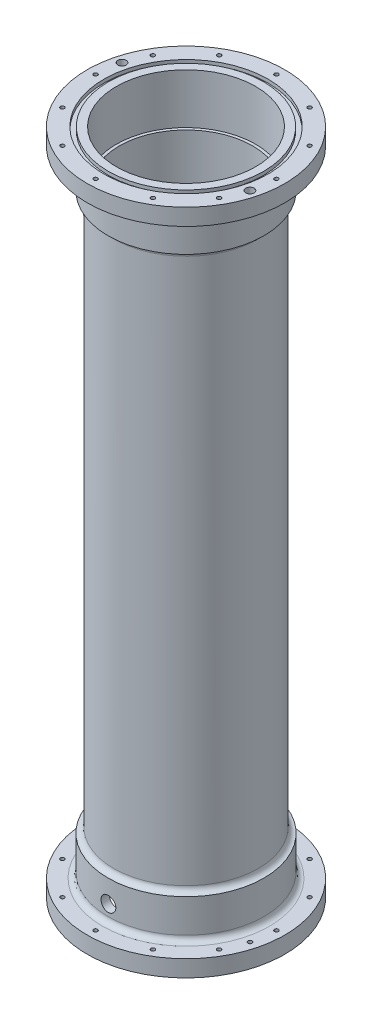
SolidWorks part; units mm, degrees
material "7075-T6 (SN)"
ref_plane "Front Plane" through (0, 0, 0) normal (0, 0, 1) x (1, 0, 0)
ref_plane "Top Plane" through (0, 0, 0) normal (0, 1, 0) x (1, 0, 0)
ref_plane "Right Plane" through (0, 0, 0) normal (1, 0, 0) x (0, 0, -1)
sketch "Sketch2" plane through (0, 0, 0) normal (0, 1, 0) x (1, 0, 0)
  circle A0 centre (0, 0) radius 38.1
  circle A1 centre (0, 0) radius 41.275
  dimension "D1" = 82.55
  dimension "D2" = 76.2
extrude "Base Cylinder" add sketch "Sketch2" along normal blind 381
sketch "Sketch3" plane through (0, 0, 0) normal (0, -1, 0) x (1, 0, 0)
  circle A0 centre (0, 0) radius 38.1
  circle A1 centre (0, 0) radius 56.3562
  dimension "D1" = 112.7125
extrude "Aft Flange" add sketch "Sketch3" against normal blind 9.525
sketch "Sketch34" plane through (0, 0, 0) normal (0, -1, 0) x (1, 0, 0)
  circle A0 centre (0, 0) radius 39.75
  dimension "D1" = 79.5
extrude "TemperatureInsert" cut sketch "Sketch34" against normal blind 28.575
sketch "Sketch6" plane through (0, 0, 0) normal (0, -1, 0) x (1, 0, 0)
  circle A0 centre (0, 0) radius 46.9011
  circle A1 centre (0, 0) radius 44.2849
  dimension "D1" = 93.8022
  dimension "D2" = 88.5698
extrude "Aft O-Ring" cut sketch "Sketch6" against normal blind 1.9812
sketch "Sketch33" plane through (0, 9.525, 0) normal (0, 1, 0) x (1, 0, 0)
  circle A0 centre (0, 0) radius 41.275
  circle A1 centre (0, 0) radius 44.45
  dimension "D1" = 82.55
  dimension "D2" = 88.9
extrude "CriticalBoss" add sketch "Sketch33" along normal blind 22.225
fillet "Fillet1" radius 3.175 2 edges at (0, 9.525, -44.45) (0, 31.75, 41.275)
sketch "Sketch For Bolt Holes" plane through (0, 0, 0) normal (0, -1, 0) x (1, 0, 0)
  circle A0 centre (-51.6255, 0) radius 1.5875
  circle A1 centre (-44.709, 25.8128) radius 1.5875
  circle A2 centre (-25.8128, 44.709) radius 1.5875
  circle A3 centre (0, 51.6255) radius 1.5875
  circle A4 centre (25.8127, 44.709) radius 1.5875
  circle A5 centre (44.709, 25.8128) radius 1.5875
  circle A6 centre (51.6255, 0) radius 1.5875
  circle A7 centre (44.709, -25.8127) radius 1.5875
  circle A8 centre (25.8128, -44.709) radius 1.5875
  circle A9 centre (0, -51.6255) radius 1.5875
  circle A10 centre (-25.8127, -44.709) radius 1.5875
  circle A11 centre (-44.709, -25.8128) radius 1.5875
  point P36 (0, 0)
  dimension "D2" = 3.175
  dimension "D1" = 51.6255
  dimension "D3" = 12
hole_wizard "Bolt Circle" positions "Sketch8" profile "Sketch9" hole size "#4-40" standard "ANSI Inch" end condition up to next
sketch "Sketch8" plane through (0, 0, 0) normal (0, -1, 0) x (-1, 0, 0)
  point P0 (-25.8127, -44.709)
  point P3 (-44.709, -25.8128)
  point P6 (-51.6255, 0)
  point P9 (-44.709, 25.8127)
  point P12 (-25.8128, 44.709)
  point P15 (0, 51.6255)
  point P18 (25.8127, 44.709)
  point P21 (44.709, 25.8128)
  point P24 (51.6255, 0)
  point P27 (44.709, -25.8128)
  point P30 (25.8128, -44.709)
  point P33 (0, -51.6255)
  point P36 (-25.8127, -44.709)
  point P38 (-44.709, -25.8128)
  point P40 (-51.6255, 0)
sketch "Sketch9" plane through (25.8127, 0, 44.709) normal (1, 0, 0) x (0, 0, -1)
  line L0 (0, 0) -> (0, 381)
  line L1 (0, 381) -> (1.1303, 381)
  line L2 (1.1303, 381) -> (1.1303, 0)
  line L5 (1.1303, 0) -> (0, 0)
  line L11 (0, -6.35) -> (0, 107.95) construction
  dimension "Thru Hole Dia." = 2.2606
  dimension "Thru Hole Depth" = 381
sketch "Dowel Hole Sketch" plane through (0, 0, 0) normal (0, -1, 0) x (1, 0, 0)
  line L0 (0, 0) -> (-51.6255, 0) construction
  line L1 (0, 0) -> (-49.8664, -13.3617) construction
  line L2 (0, 0) -> (0, -51.6255) construction
  line L3 (0, 0) -> (49.8664, 13.3617) construction
  circle A0 centre (0, 0) radius 51.6255
  circle A1 centre (-49.8664, -13.3617) radius 4.6172
  circle A2 centre (49.8664, 13.3617) radius 3.4532
  dimension "D1" = 15
hole_wizard "Hole1" positions "Sketch14" profile "Sketch12" legacy end condition up to next
sketch "Sketch14" plane through (0, 0, 0) normal (0, -1, 0) x (-1, 0, 0)
  point P0 (49.8664, 13.3617)
  point P3 (-49.8664, -13.3617)
sketch "Sketch12" plane through (-49.8664, 0, -13.3617) normal (1, 0, 0) x (0, 0, -1)
  line L0 (0, 0) -> (0, 381)
  line L1 (0, 381) -> (1.1906, 381)
  line L2 (1.1906, 381) -> (1.1906, 4.7625)
  line L3 (1.1906, 4.7625) -> (2.3813, 4.7625)
  line L4 (2.3813, 4.7625) -> (2.3813, 0)
  line L5 (2.3813, 0) -> (0, 0)
  line L6 (0, 110) -> (0, -10) construction
  dimension "Diameter" = 2.3813
  dimension "Depth" = 381
  dimension "C-Bore Diameter" = 4.7625
  dimension "C-Bore Depth" = 4.7625
ref_plane "Hoop Mid-Plane" through (0, 190.5, 0) normal (0, 1, 0) x (1, 0, 0)
ref_plane "PressureTapHolePlane" through (0, 0, 44.45) normal (0, 0, 1) x (1, 0, 0)
ref_plane "TemperatureTapPlane" through (0, 0, -44.45) normal (0, 0, 1) x (1, 0, 0)
sketch "ThermoHole" plane through (0, 0, -44.45) normal (0, 0, 1) x (1, 0, 0)
  line L0 (-56.3562, 0) -> (56.3562, 0) construction
  circle A0 centre (0, 19.05) radius 3.175
  dimension "D1" = 19.05
  dimension "D2" = 6.35
hole_wizard "1/8 NPT Tapped ThermocoupleHole" positions "Sketch43" profile "Sketch44" size "1/8" standard "ANSI Inch"
sketch "Sketch43" plane through (0, 0, -44.45) normal (0, 0, 1) x (1, 0, 0)
  line L0 (-56.3562, 0) -> (56.3562, 0) construction
  point P0 (0, 19.05)
  dimension "D1" = 19.05
sketch "Sketch44" plane through (0, 19.05, -44.45) normal (1, 0, 0) x (0, 1, 0)
  line L0 (0, 0) -> (0, 14.2175)
  line L1 (4.2164, 11.684) -> (0, 14.2175)
  line L2 (-4.2164, 11.684) -> (0, 14.2175) construction
  line L3 (4.2164, 11.684) -> (4.2164, 6.858)
  line L4 (4.2164, 6.858) -> (4.9362, 6.858)
  line L5 (4.9362, 6.858) -> (5.1415, 0)
  line L6 (-4.9362, 6.858) -> (-5.1415, 0) construction
  line L7 (5.1415, 0) -> (0, 0)
  line L8 (0, -6.35) -> (0, 107.95) construction
  line L11 (-4.2164, 6.858) -> (-4.9362, 6.858) construction
  dimension "Tap Drill Dia." = 8.4328
  dimension "Tap Drill Depth" = 11.684
  dimension "Thread Dia." = 10.283
  dimension "Thread Angle" = 3.43
  dimension "Thread Depth" = 6.858
  dimension "Drill Angle" = 118
mirror "Mirror1" about plane through (0, 190.5, 0) normal (0, 1, 0) of "Hole1", "Bolt Circle", "Fillet1", "CriticalBoss", "Aft O-Ring", "TemperatureInsert", "Aft Flange"
hole_wizard "3/8-24 Tapped Hole1" positions "Sketch48" profile "Sketch49" tap size "3/8-24" standard "ANSI Inch" end condition up to next
sketch "Sketch48" plane through (0, 0, 44.45) normal (0, 0, 1) x (1, 0, 0)
  line L0 (-56.3562, 0) -> (56.3562, 0) construction
  point P0 (0, 19.05)
  dimension "D1" = 19.05
sketch "Sketch49" plane through (0, 19.05, 44.45) normal (1, 0, 0) x (0, -1, 0)
  line L0 (0, 0) -> (0, 4.7)
  line L1 (0, 4.7) -> (4.2164, 4.7)
  line L2 (4.2164, 4.7) -> (4.2164, 0)
  line L5 (4.2164, 0) -> (0, 0)
  line L11 (0, -6.35) -> (0, 107.95) construction
  dimension "Thru Tap Drill Dia." = 8.4328
  dimension "Thru Tap Drill Depth" = 4.7
cosmetic thread "Hole Thread1" parameters "D2"=9.525
